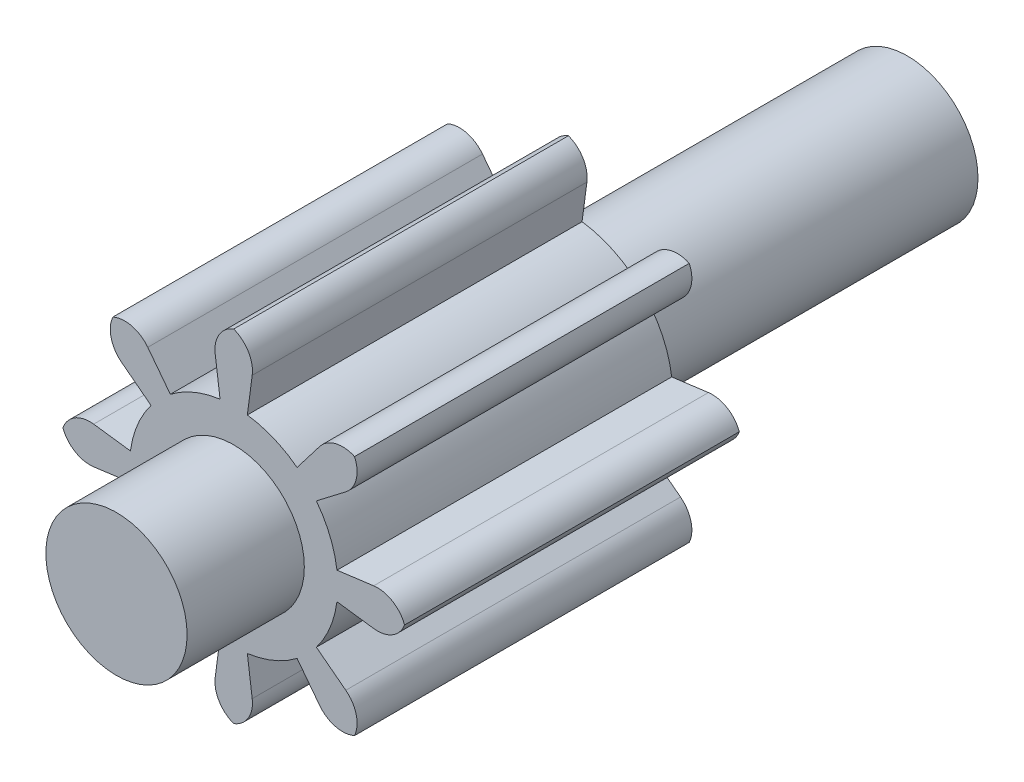
SolidWorks part; units mm, degrees
material "AISI 347 Annealed Stainless Steel (SS)"
ref_plane "Front Plane" through (0, 0, 0) normal (0, 0, 1) x (1, 0, 0)
ref_plane "Top Plane" through (0, 0, 0) normal (0, 1, 0) x (1, 0, 0)
ref_plane "Right Plane" through (0, 0, 0) normal (1, 0, 0) x (0, 0, -1)
sketch "Sketch1" plane through (0, 0, 0) normal (0, 0, 1) x (1, 0, 0)
  line L0 (0, -1.6956) -> (0, 1.7606) construction
  line L1 (-0.0966, 0.7311) -> (-0.131, 0.9914)
  line L2 (0.0966, 0.7311) -> (0.131, 0.9914)
  line L3 (0.5853, 0.4487) -> (0.7936, 0.6084)
  line L4 (0.4487, 0.5853) -> (0.6084, 0.7936)
  line L5 (0.7311, -0.0966) -> (0.9914, -0.131)
  line L6 (0.7311, 0.0966) -> (0.9914, 0.131)
  line L7 (0.4487, -0.5853) -> (0.6084, -0.7936)
  line L8 (0.5853, -0.4487) -> (0.7936, -0.6084)
  line L9 (-0.0966, -0.7311) -> (-0.131, -0.9914)
  line L10 (0.0966, -0.7311) -> (0.131, -0.9914)
  line L11 (-0.5853, -0.4487) -> (-0.7936, -0.6084)
  line L12 (-0.4487, -0.5853) -> (-0.6084, -0.7936)
  line L13 (-0.7311, 0.0966) -> (-0.9914, 0.131)
  line L14 (-0.7311, -0.0966) -> (-0.9914, -0.131)
  line L15 (-0.4487, 0.5853) -> (-0.6084, 0.7936)
  line L16 (-0.5853, 0.4487) -> (-0.7936, 0.6084)
  arc A0 (-0.5853, 0.4487) -> (-0.7311, 0.0966) centre (0, 0) ccw
  arc A1 (-0.0966, 0.7311) -> (-0.4487, 0.5853) centre (0, 0) ccw
  arc A2 (0.4487, 0.5853) -> (0.0966, 0.7311) centre (0, 0) ccw
  arc A3 (-0.131, 0.9914) -> (0, 1.21) centre (0.0722, 1.0182) cw
  arc A4 (0.131, 0.9914) -> (0, 1.21) centre (-0.0722, 1.0182) ccw
  arc A5 (0.6084, 0.7936) -> (0.8556, 0.8556) centre (0.771, 0.669) cw
  arc A6 (0.7936, 0.6084) -> (0.8556, 0.8556) centre (0.669, 0.771) ccw
  arc A7 (0.9914, 0.131) -> (1.21, 0) centre (1.0182, -0.0722) cw
  arc A8 (0.9914, -0.131) -> (1.21, 0) centre (1.0182, 0.0722) ccw
  arc A9 (0.7936, -0.6084) -> (0.8556, -0.8556) centre (0.669, -0.771) cw
  arc A10 (0.6084, -0.7936) -> (0.8556, -0.8556) centre (0.771, -0.669) ccw
  arc A11 (0.131, -0.9914) -> (0, -1.21) centre (-0.0722, -1.0182) cw
  arc A12 (-0.131, -0.9914) -> (0, -1.21) centre (0.0722, -1.0182) ccw
  arc A13 (-0.6084, -0.7936) -> (-0.8556, -0.8556) centre (-0.771, -0.669) cw
  arc A14 (-0.7936, -0.6084) -> (-0.8556, -0.8556) centre (-0.669, -0.771) ccw
  arc A15 (-0.9914, -0.131) -> (-1.21, 0) centre (-1.0182, 0.0722) cw
  arc A16 (-0.9914, 0.131) -> (-1.21, 0) centre (-1.0182, -0.0722) ccw
  arc A17 (-0.7936, 0.6084) -> (-0.8556, 0.8556) centre (-0.669, 0.771) cw
  arc A18 (-0.6084, 0.7936) -> (-0.8556, 0.8556) centre (-0.771, 0.669) ccw
  arc A19 (0.7311, 0.0966) -> (0.5853, 0.4487) centre (0, 0) ccw
  arc A20 (-0.7311, -0.0966) -> (-0.5853, -0.4487) centre (0, 0) ccw
  arc A21 (-0.4487, -0.5853) -> (-0.0966, -0.7311) centre (0, 0) ccw
  arc A22 (0.0966, -0.7311) -> (0.4487, -0.5853) centre (0, 0) ccw
  arc A23 (0.5853, -0.4487) -> (0.7311, -0.0966) centre (0, 0) ccw
  circle A24 centre (0, 0) radius 0.5
  point P65 (0, 0)
  dimension "D1" = 2.42
  dimension "D2" = 1.475
  dimension "D3" = 1
  dimension "D4" = 8
extrude "Boss-Extrude1" add sketch "Sketch1" along normal blind 2.37
extrude "Boss-Extrude3" add sketch "Sketch1<3>" along normal blind 3.2 and the other way blind 2.4 contours A24 L0 | L0 A24 region at (-0.2122, 0, 0) region at (0.2122, 0, 0)
sketch "Sketch1<3>" plane through (0, 0, 0) normal (0, 0, 1) x (1, 0, 0) same geometry as "Sketch1"
